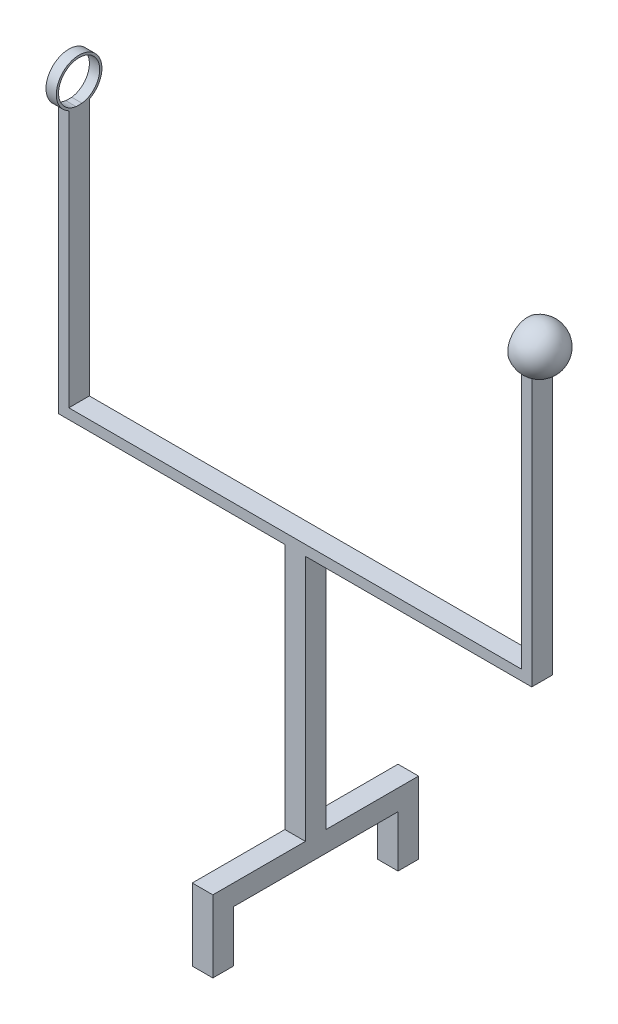
SolidWorks part; units mm, degrees
ref_plane "Plan de face" through (0, 0, 0) normal (0, 0, 1) x (1, 0, 0)
ref_plane "Plan de dessus" through (0, 0, 0) normal (0, 1, 0) x (1, 0, 0)
ref_plane "Plan de droite" through (0, 0, 0) normal (1, 0, 0) x (0, 0, -1)
sketch "Esquisse1" plane through (0, 0, 0) normal (0, 0, 1) x (1, 0, 0)
  line L0 (0, 0) -> (0, 50)
  line L1 (0, 50) -> (44, 50)
  line L2 (44, 50) -> (44, 100)
  line L3 (44, 100) -> (46, 100)
  line L4 (46, 100) -> (46, 48)
  line L5 (46, 48) -> (2, 48)
  line L6 (2, 48) -> (2, 0)
  line L7 (2, 0) -> (0, 0)
  point P5 (46, 48)
  point P10 (0, 0)
  dimension "D1" = 2
  dimension "D2" = 2
  dimension "D3" = 2
  dimension "D4" = 44
  dimension "D5" = 50
  dimension "D6" = 50
extrude "Boss.-Extru.1" add sketch "Esquisse1" along normal blind 2 and the other way blind 2
sketch "Esquisse2" plane through (0, 0, 0) normal (0, 0, 1) x (1, 0, 0)
  line L0 (45.4807, 104) -> (46.4871, 104) construction
  line L1 (46, 100) -> (44, 100) construction
  line L2 (45.4807, 104) -> (41.7785, 110.4123) construction
  line L3 (43.4807, 107.4641) -> (43.2307, 107.8971)
  line L4 (49.9807, 104) -> (49.4807, 104)
  arc A0 (43.2307, 107.8971) -> (49.9807, 104) centre (45.4807, 104) cw
  arc A1 (43.4807, 107.4641) -> (49.4807, 104) centre (45.4807, 104) cw
  dimension "D2" = 4.5
  dimension "D3" = 4
  dimension "D1" = 4
  dimension "D4" = 120
revolve "Révolution1" add sketch "Esquisse2" angle 360 about L4
mirror "Symétrie1" about plane through (0, 0, -2) normal (-1, 0, 0) of "Boss.-Extru.1"
sketch "Esquisse3" plane through (0, 0, 0) normal (0, 0, 1) x (1, 0, 0)
  line L1 (-2, -4) -> (2, -4)
  line L2 (-2, -4) -> (-2, 0)
  line L3 (-2, 0) -> (2, 0)
  line L4 (2, -4) -> (2, 0)
  line L5 (-2, -4) -> (2, 0) construction
  line L6 (-2, 0) -> (2, -4) construction
  point P0 (0, -2)
  point P6 (-2, -2)
  dimension "D1" = 2
  dimension "D2" = 4
extrude "Boss.-Extru.2" add sketch "Esquisse3" along normal blind 20
sketch "Esquisse4" plane through (0, -4, 0) normal (0, -1, 0) x (-1, 0, 0)
  line L0 (-2, -20) -> (-2, 0) construction
  line L1 (2, -20) -> (-2, -20)
  line L2 (2, -20) -> (2, -16)
  line L3 (2, -16) -> (-2, -16)
  line L4 (-2, -20) -> (-2, -16)
  dimension "D1" = 4
extrude "Boss.-Extru.3" add sketch "Esquisse4" along normal blind 10
mirror "Symétrie2" about plane through (0, 0, 0) normal (0, 0, -1) of "Boss.-Extru.2", "Boss.-Extru.3"
sketch "Esquisse5" plane through (-46, 0, 0) normal (-1, 0, 0) x (0, 0, 1)
  circle A0 centre (0, 103.9587) radius 4.4352
  circle A1 centre (0, 103.9587) radius 4
  dimension "D1" = 8.8704
  dimension "D2" = 8
extrude "Boss.-Extru.4" add sketch "Esquisse5" against normal up to surface (2 mm away) up to face at (-44, 75, 0)
